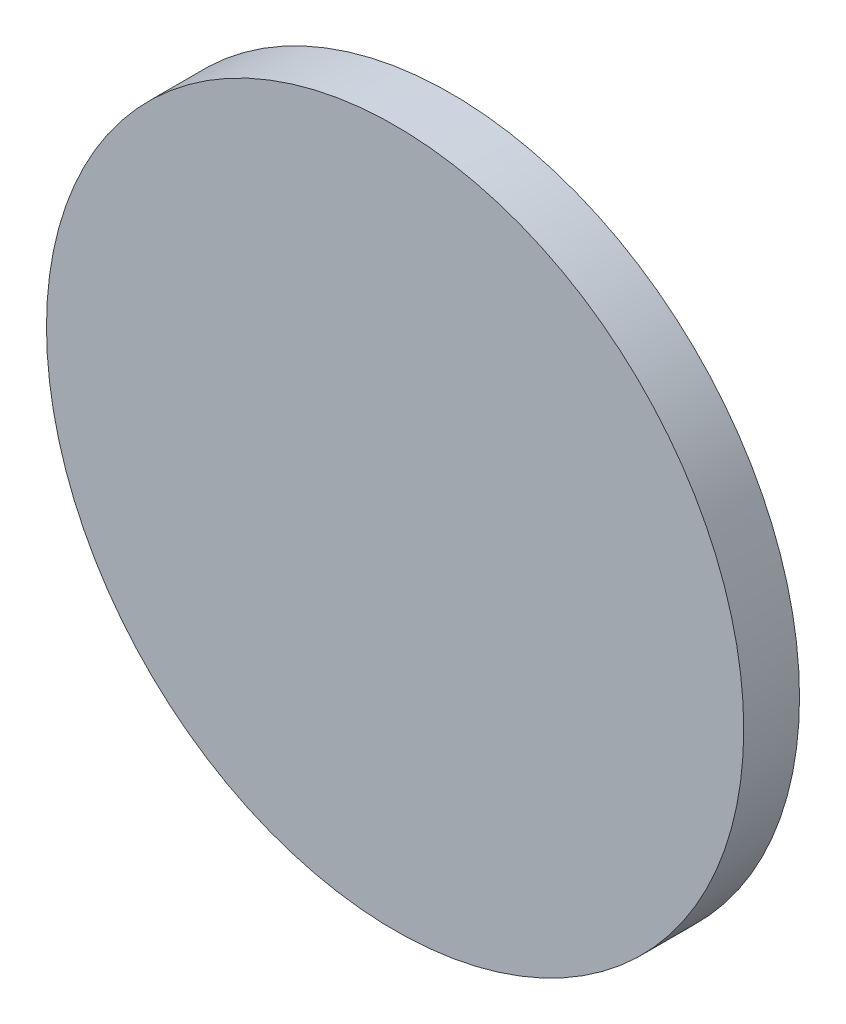
SolidWorks part; units mm, degrees
ref_plane "Front Plane" through (0, 0, 0) normal (0, 0, 1) x (1, 0, 0)
ref_plane "Top Plane" through (0, 0, 0) normal (0, 1, 0) x (1, 0, 0)
ref_plane "Right Plane" through (0, 0, 0) normal (1, 0, 0) x (0, 0, -1)
sketch "Sketch1" plane through (0, 0, 0) normal (0, 0, 1) x (1, 0, 0)
  circle A0 centre (0, 0) radius 12.5
  point P4 (0, 0)
  dimension "D1" = 25
extrude "Boss-Extrude1" add sketch "Sketch1" along normal blind 2
ref_axis "Axis1" through (0, 0, 0) along (0, 0, -1)
